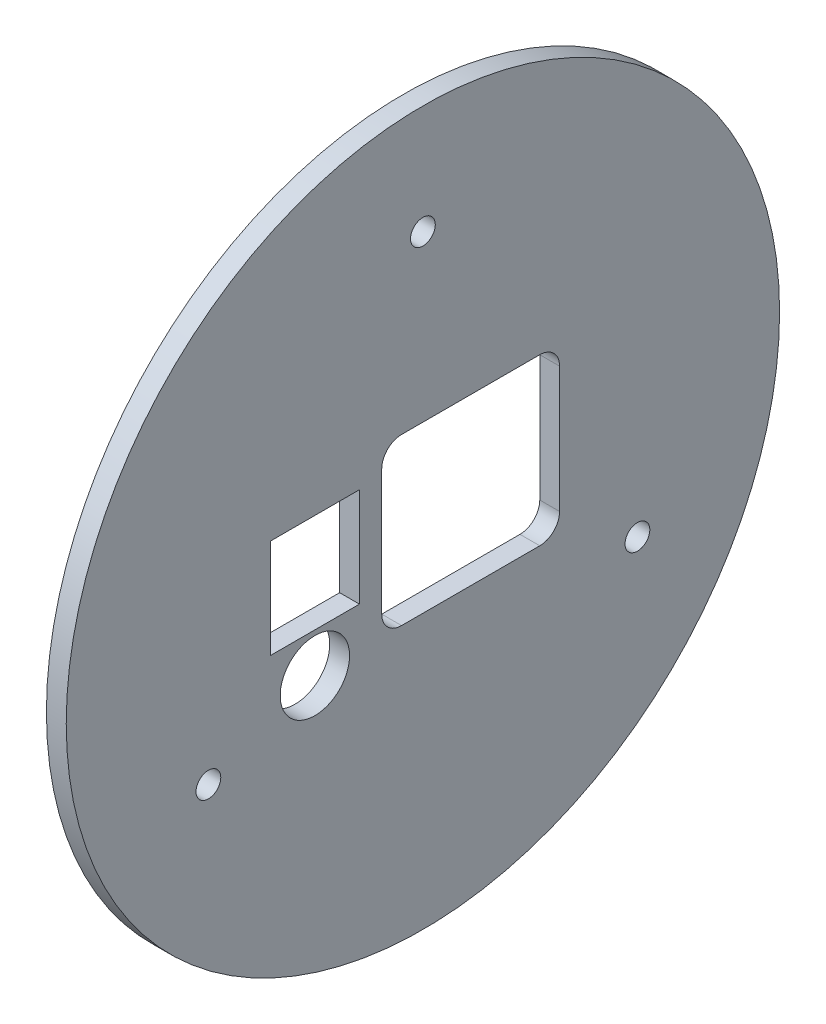
SolidWorks part; units mm, degrees
ref_plane "Front Plane" through (0, 0, 0) normal (0, 0, 1) x (1, 0, 0)
ref_plane "Top Plane" through (0, 0, 0) normal (0, 1, 0) x (1, 0, 0)
ref_plane "Right Plane" through (0, 0, 0) normal (1, 0, 0) x (0, 0, -1)
sketch "Sketch1" plane through (0, 0, 0) normal (1, 0, 0) x (0, 0, -1)
  line L0 (-72, 0) -> (72, 0) construction
  line L1 (-4.3098, 16.7) -> (23.5902, 16.7)
  line L2 (-8.3098, 12.7) -> (-8.3098, -12.7)
  line L3 (-4.3098, -16.7) -> (23.5902, -16.7)
  line L4 (27.5902, 12.7) -> (27.5902, -12.7)
  line L5 (4.2715, -16.7) -> (-70.0365, -16.7) construction
  line L6 (-21.8098, -16.7) -> (-21.8098, 68.6173) construction
  line L7 (-30.8098, 11.3) -> (-12.8098, 11.3)
  line L8 (-30.8098, 11.3) -> (-30.8098, -8.7)
  line L9 (-30.8098, -8.7) -> (-12.8098, -8.7)
  line L10 (-12.8098, 11.3) -> (-12.8098, -8.7)
  line L11 (0, 72) -> (0, -72) construction
  circle A0 centre (0, 0) radius 72
  circle A1 centre (-21.8098, -16.7) radius 7
  circle A2 centre (0, 50) radius 2.5
  circle A3 centre (43.3013, -25) radius 2.5
  circle A4 centre (-43.3013, -25) radius 2.5
  arc A5 (-4.3098, -16.7) -> (-8.3098, -12.7) centre (-4.3098, -12.7) cw
  arc A6 (23.5902, -16.7) -> (27.5902, -12.7) centre (23.5902, -12.7) ccw
  arc A7 (27.5902, 12.7) -> (23.5902, 16.7) centre (23.5902, 12.7) ccw
  arc A8 (-4.3098, 16.7) -> (-8.3098, 12.7) centre (-4.3098, 12.7) ccw
  point P13 (0, 0)
  point P29 (-8.3098, -16.7)
  point P32 (27.5902, -16.7)
  point P35 (27.5902, 16.7)
  point P38 (-8.3098, 16.7)
  dimension "D1" = 144
  dimension "D2" = 35.9
  dimension "D3" = 5
  dimension "D7" = 14
  dimension "D12" = 4
  dimension "D4" = 50
  dimension "D6" = 33.4
  dimension "D8" = 13.5
  dimension "D9" = 18
  dimension "D10" = 20
  dimension "D11" = 8
  dimension "D5" = 3
extrude "Boss-Extrude1" add sketch "Sketch1" along normal blind 4
